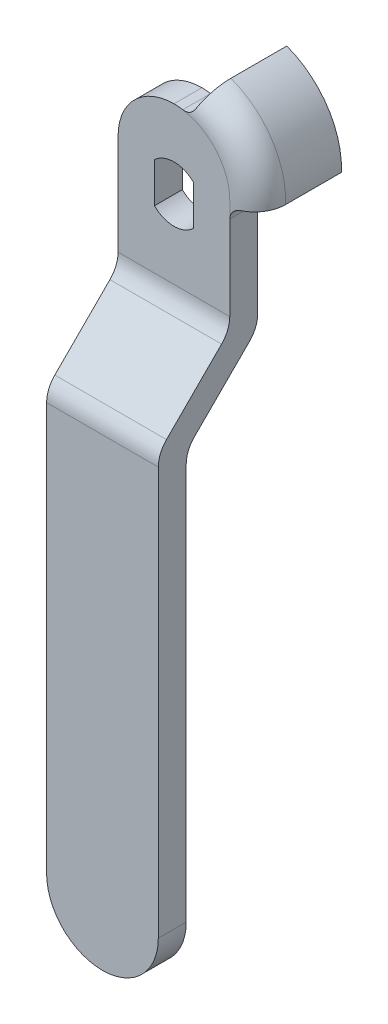
SolidWorks part; units mm, degrees
material "Galvanized Steel"
ref_plane "Płaszczyzna przednia" through (0, 0, 0) normal (1, 0, 0) x (0, 1, 0)
ref_plane "Płaszczyzna górna" through (0, 0, 0) normal (0, 0, 1) x (0, 1, 0)
ref_plane "Płaszczyzna prawa" through (0, 0, 0) normal (0, 1, 0) x (-1, 0, 0)
ref_axis "Axis1" through (0, -5, -43.2) along (0, 0, 1)
sketch "Szkic2" plane through (0, 0, 0) normal (1, 0, 0) x (0, 1, 0)
  line L0 (0, 0) -> (-21.0711, 0)
  line L1 (-24.6066, 1.4645) -> (-34.4777, 11.3355)
  line L2 (-38.0132, 12.8) -> (-119, 12.8)
  line L3 (-119, 12.8) -> (-119, 17.8)
  line L4 (-119, 17.8) -> (-35.9421, 17.8)
  line L5 (-32.4066, 16.3355) -> (-22.5355, 6.4645)
  line L6 (-19, 5) -> (9, 5)
  line L8 (9, 5) -> (9, 0)
  line L9 (9, 0) -> (0, 0)
  line L10 (-5, -43.2) -> (-5, 8.5) construction
  arc A0 (-22.5355, 6.4645) -> (-19, 5) centre (-19, 10) ccw
  arc A1 (-21.0711, 0) -> (-24.6066, 1.4645) centre (-21.0711, 5) cw
  arc A2 (-35.9421, 17.8) -> (-32.4066, 16.3355) centre (-35.9421, 12.8) cw
  arc A3 (-34.4777, 11.3355) -> (-38.0132, 12.8) centre (-38.0132, 7.8) ccw
  point P14 (-21.0711, 5)
  point P19 (-33.8711, 17.8)
  dimension "D8" = 5
  dimension "D2" = 135
  dimension "D3" = 5
  dimension "D4" = 5
  dimension "D5" = 5
  dimension "D6" = 28
  dimension "D9" = 12.8
  dimension "D10" = 14
  dimension "D11" = 114
extrude "Dodanie-wyciągnięcie1" add sketch "Szkic2" along normal mid plane 20
fillet "Zaokrąglenie1" radius 10 4 edges at (10, -119, 15.3) (-10, -119, 15.3) (-10, 9, 2.5) (10, 9, 2.5)
ref_axis "Axis3" through (0, 9, 0) along (0, -0.995, 0.0995)
sketch "Szkic8" plane through (0, 0, 0) normal (0, 0, 1) x (0, 1, 0)
  line L0 (7.8243, 0) -> (-16.4934, 0) construction
  line L5 (-1.4293, 3.5) -> (-8.5707, 3.5)
  line L6 (-8.5707, -3.5) -> (-1.4293, -3.5)
  arc A2 (-8.5707, 3.5) -> (-8.5707, -3.5) centre (-5, 0) ccw
  arc A3 (-1.4293, -3.5) -> (-1.4293, 3.5) centre (-5, 0) ccw
  dimension "D5" = 10
  dimension "D1" = 7
extrude "Wytnij-wyciągnięcie3" cut sketch "Szkic8" along normal through all
ref_point "Point1"
sketch "Sketch1" plane through (0, 0, 0) normal (0, 0, 1) x (0, 1, 0)
  line L0 (-5, 0) -> (-2, 0) construction
  line L1 (-2, 0) -> (-2, -10) construction
  line L2 (-1, -10) -> (-19, -10) construction
  line L3 (-5, 0) -> (-5, -3) construction
  line L4 (-5, -3) -> (8.5394, -3) construction
  line L5 (2.2155, -9.4689) -> (-1, 0) construction
  line L6 (6.7554, -6.313) -> (-1, 0) construction
  line L7 (-2, -9.9499) -> (-1.6478, -14.986)
  line L8 (13.0668, -5.2082) -> (8.5394, -3)
  line L9 (-21.0711, -10) -> (-1, -10) construction
  arc A0 (-1, -10) -> (9, 0) centre (-1, 0) ccw construction
  arc A1 (-1.6478, -14.986) -> (13.0668, -5.2082) centre (-1, 0) ccw
  arc A4 (-2, -9.9499) -> (8.5394, -3) centre (-1, 0) ccw
  dimension "D3" = 30
  dimension "D1" = 3
  dimension "D2" = 3
  dimension "D4" = 94
  dimension "D5" = 154
extrude "Boss-Extrude1" add sketch "Sketch1" against normal blind 15 from surface starting at face at (0, -5.3716, 5)
sketch "Sketch3" plane through (0, 0, -10) normal (0, 0, -1) x (1, 0, 0)
  circle A1 centre (0, 1) radius 12.5
  dimension "D1" = 25
extrude "Cut-Extrude1" cut sketch "Sketch3" against normal up to surface (10 mm away) up to face at (0, -5, 0)
fillet "Fillet3" radius 5 1 edges at (12.4933, 7.3017, 5)
fillet "Fillet2" radius 2 2 edges at (10, -1.9965, 2.4999) (3, 8.5394, 2.5)
fillet "Fillet4" radius 2 1 edges at (10.4207, 5.9035, 0)
